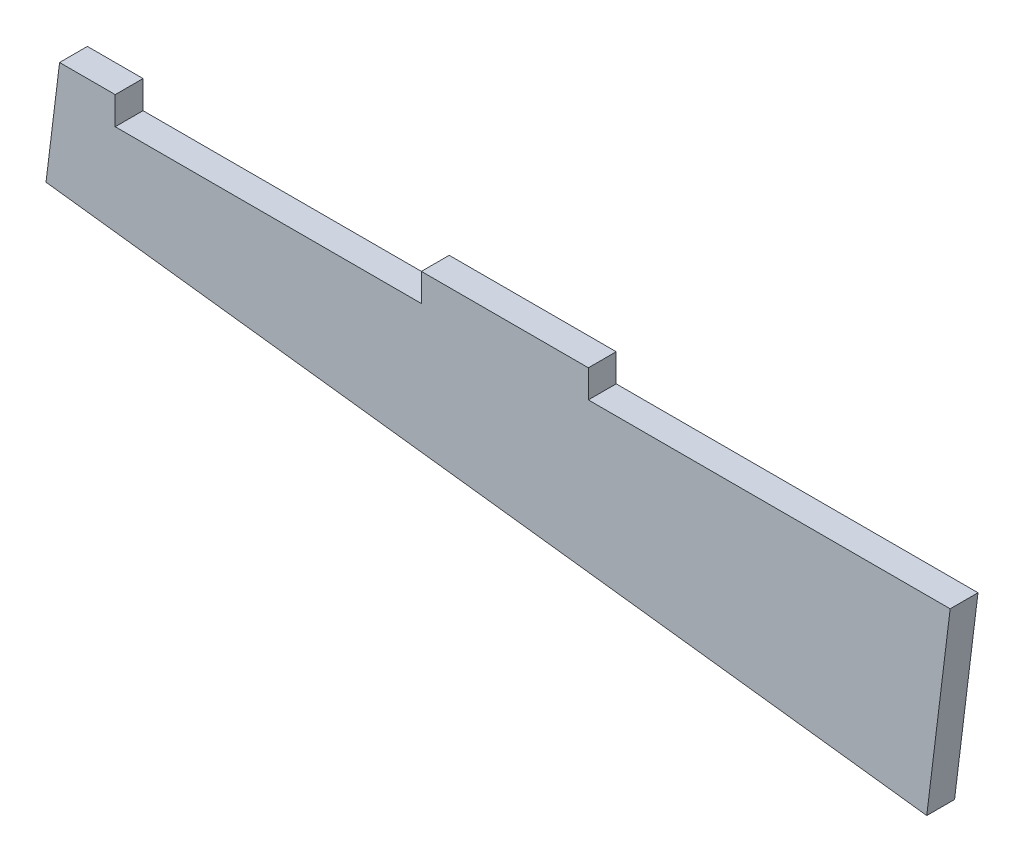
SolidWorks part; units mm, degrees
ref_plane "Front Plane" through (0, 0, 0) normal (0, 0, 1) x (1, 0, 0)
ref_plane "Top Plane" through (0, 0, 0) normal (0, 1, 0) x (1, 0, 0)
ref_plane "Right Plane" through (0, 0, 0) normal (1, 0, 0) x (0, 0, -1)
sketch "Sketch1" plane through (0, 0, 0) normal (0, 0, 1) x (1, 0, 0)
  line L0 (-195.3168, -62.6592) -> (-182.6168, -62.6592)
  line L4 (-182.6168, -62.6592) -> (-182.6168, -69.0092)
  line L5 (-182.6168, -69.0092) -> (-112.7668, -69.0092)
  line L6 (-112.7668, -69.0092) -> (-112.7668, -62.6592)
  line L7 (-112.7668, -62.6592) -> (-74.6668, -62.6592)
  line L8 (-74.6668, -62.6592) -> (-74.6668, -69.0092)
  line L9 (-74.6668, -69.0092) -> (7.8832, -69.0092)
  line L10 (7.8832, -69.0092) -> (2.5379, -112.5435)
  line L11 (2.5379, -112.5435) -> (-198.4122, -87.8699)
  line L12 (-198.4122, -87.8699) -> (-195.3168, -62.6592)
  line L13 (-383.9577, -53.3922) -> (9.7423, -101.7325) construction
  dimension "D1" = 12.7
  dimension "D2" = 6.35
  dimension "D3" = 69.85
  dimension "D4" = 38.1
  dimension "D5" = 82.55
  dimension "D6" = 25.4
extrude "Boss-Extrude1" add sketch "Sketch1" against normal blind 6.35
